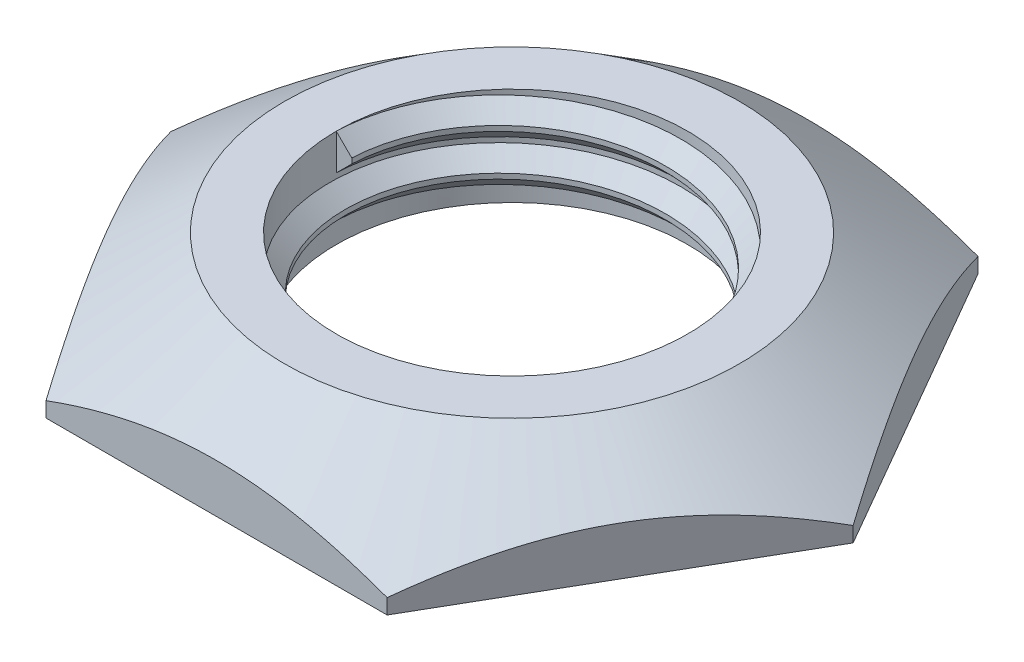
SolidWorks part; units mm, degrees
ref_plane "前视基准面" through (0, 0, 0) normal (0, 0, 1) x (1, 0, 0)
ref_plane "上视基准面" through (0, 0, 0) normal (0, 1, 0) x (1, 0, 0)
ref_plane "右视基准面" through (0, 0, 0) normal (1, 0, 0) x (0, 0, -1)
sketch "草图1" plane through (0, 0, 0) normal (0, 0, 1) x (1, 0, 0)
  line L0 (0, 0) -> (0, -9.5)
  line L1 (0, -9.5) -> (-35, -9.5)
  line L2 (-35, -9.5) -> (-22, 0)
  line L3 (-22, 0) -> (0, 0)
  line L4 (0, -4.75) -> (-27.5, -4.75) construction
  point P7 (0, 0)
  dimension "D1" = 9.5
  dimension "D2" = 22
  dimension "D3" = 35
  dimension "D4" = 27.5
revolve "旋转1" add sketch "草图1" angle 360 about L0
sketch "草图4" plane through (0, 0, 0) normal (0, 1, 0) x (1, 0, 0)
  circle A0 centre (0, 0) radius 17
  circle A1 centre (0, 0) radius 22 construction
  dimension "D1" = 5
extrude "切除-拉伸2" cut sketch "草图4" against normal blind 10
ref_plane "基准面1" through (0, -7.75, 0) normal (0, -1, 0) x (-1, 0, 0)
sketch "草图6" plane through (0, -7.75, 0) normal (0, -1, 0) x (-1, 0, 0)
  circle A0 centre (0, 0) radius 17 construction
  circle A1 centre (0, 0) radius 17
curve "螺旋线/涡状线2" pitch 4 height 6 radius 17 centre (0, -7.75, 0) axis (0, 1, 0) start towards (1, 0, 0)
sketch "草图7" plane through (0, 0, 0) normal (0, 0, 1) x (1, 0, 0)
  line L0 (17, -6) -> (17, -9.5)
  line L1 (17, -9.5) -> (15.5, -8)
  line L2 (15.5, -8) -> (15.5, -7.5)
  line L3 (15.5, -7.5) -> (17, -6)
  point P3 (17, -7.75)
  dimension "D1" = 3.5
  dimension "D2" = 1.5
  dimension "D3" = 45
sweep "扫描1" add profiles "草图7" path "螺旋线/涡状线2"
sketch "草图12" plane through (0, 0, 0) normal (1, 0, 0) x (0, 0, -1)
  line L0 (-34, -8.7692) -> (-34, -9.5)
  line L1 (-22, 0) -> (-35, -9.5) construction
  line L2 (-35, -9.5) -> (35, -9.5) construction
  line L3 (-34, -8.7692) -> (-35, -8.7692)
  line L6 (-35, -9.5) -> (-35, -8.7692)
  line L7 (-35, -9.5) -> (-34, -9.5)
  line L8 (0, 0) -> (0, 50000) construction
  dimension "D1" = 1
revolve "切除-旋转4" cut sketch "草图12" angle 360 about L8
sketch "草图13" plane through (0, -9.5, 0) normal (0, -1, 0) x (1, 0, 0)
  line L1 (-33, 0) -> (-16.5, -28.5788)
  line L2 (-16.5, -28.5788) -> (16.5, -28.5788)
  line L3 (16.5, -28.5788) -> (33, 0)
  line L4 (33, 0) -> (16.5, 28.5788)
  line L5 (16.5, 28.5788) -> (-16.5, 28.5788)
  line L6 (-16.5, 28.5788) -> (-33, 0)
  circle A0 centre (0, 0) radius 28.5788 construction
  circle A2 centre (0, 0) radius 17 construction
  circle A3 centre (0, 0) radius 34
  dimension "D1" = 33
extrude "切除-拉伸3" cut sketch "草图13" against normal blind 10
